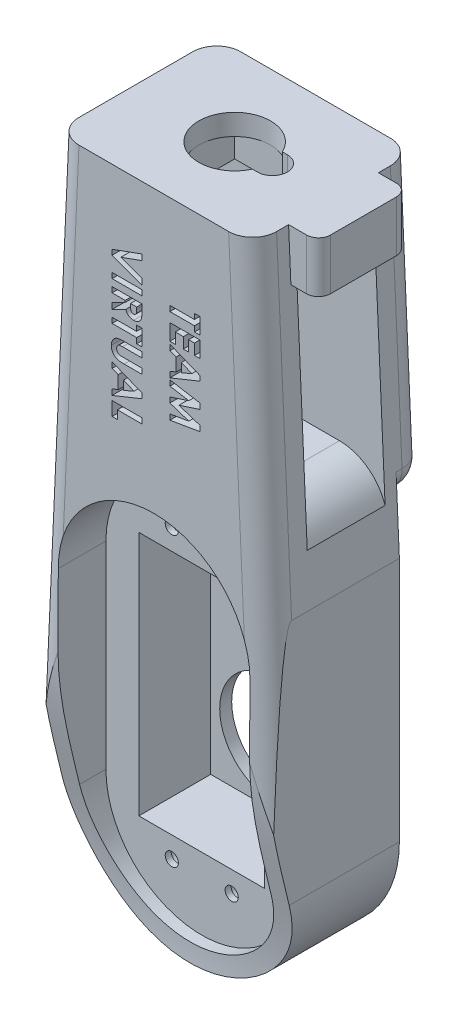
SolidWorks part; units mm, degrees
ref_plane "Front Plane" through (0, 0, 0) normal (0, 0, 1) x (1, 0, 0)
ref_plane "Top Plane" through (0, 0, 0) normal (0, 1, 0) x (1, 0, 0)
ref_plane "Right Plane" through (0, 0, 0) normal (1, 0, 0) x (0, 0, -1)
sketch "Sketch1" plane through (0, 0, 0) normal (0, 0, 1) x (1, 0, 0)
  line L5 (-19, -60) -> (19, -60)
  line L6 (-19, -60) -> (-19, 60)
  line L7 (-19, 60) -> (19, 60)
  line L8 (19, -60) -> (19, 60)
  line L9 (-19, -60) -> (19, 60) construction
  line L10 (-19, 60) -> (19, -60) construction
  line L11 (-10.5, -45) -> (10.5, -45)
  line L12 (-10.5, -45) -> (-10.5, -4)
  line L13 (-10.5, -4) -> (10.5, -4)
  line L14 (10.5, -45) -> (10.5, -4)
  line L15 (-10.5, -45) -> (10.5, -4) construction
  line L16 (-10.5, -4) -> (10.5, -45) construction
  point P0 (0, 0)
  point P6 (0, -24.5)
  dimension "D1" = 21
  dimension "D2" = 41
  dimension "D3" = 8.5
  dimension "D4" = 120
  dimension "D5" = 15
extrude "Boss-Extrude1" add sketch "Sketch1" along normal blind 11
ref_plane "Plane1" through (0, 0, 10) normal (0, 0, 1) x (1, 0, 0)
sketch "Sketch3" plane through (0, 0, 10) normal (0, 0, 1) x (1, 0, 0)
  line L0 (10.5, -4) -> (-10.5, -4) construction
  circle A0 centre (-5, -0.5) radius 1.3
  circle A1 centre (5, -0.5) radius 1.3
  circle A2 centre (5, -48.5) radius 1.3
  circle A3 centre (-5, -48.5) radius 1.3
  dimension "D1" = 2.6
  dimension "D2" = 5
  dimension "D3" = 3.5
  dimension "D4" = 2
  dimension "D5" = 2
extrude "Cut-Extrude1" cut sketch "Sketch3" against normal blind 8
fillet "Fillet3" radius 19 2 edges at (19, -60, 5.5) (-19, -60, 5.5)
sketch "Sketch4" plane through (0, 0, 11) normal (0, 0, 1) x (1, 0, 0)
  line L0 (16, -41) -> (16, 57)
  line L1 (16, 57) -> (-16, 57)
  line L2 (-16, 57) -> (-16, -41)
  line L3 (19, -41) -> (19, 60)
  line L4 (19, 60) -> (-19, 60)
  line L5 (-19, 60) -> (-19, -41)
  line L6 (19, -41) -> (19, 60)
  line L7 (19, 60) -> (-19, 60)
  line L8 (-19, 60) -> (-19, -41)
  arc A0 (-16, -41) -> (0, -57) centre (0, -41) ccw
  arc A1 (0, -57) -> (16, -41) centre (0, -41) ccw
  arc A2 (-19, -41) -> (0, -60) centre (0, -41) ccw
  arc A3 (0, -60) -> (19, -41) centre (0, -41) ccw
  arc A4 (-19, -41) -> (0, -60) centre (0, -41) ccw
  arc A5 (0, -60) -> (19, -41) centre (0, -41) ccw
  dimension "D1" = 0
  dimension "D2" = 3
extrude "Boss-Extrude2" add sketch "Sketch4" along normal blind 8
sketch "Sketch6" plane through (0, 0, 0) normal (1, 0, 0) x (0, 0, -1)
  line L7 (-13, -60) -> (-17, -35)
  line L8 (-17, -35) -> (-19, -20)
  line L9 (-19, -41) -> (-19, 60) construction
  line L10 (-19, -20) -> (-19, -60)
  line L11 (-19, -41) -> (-19, -60) construction
  line L12 (-19, -60) -> (-13, -60)
  line L13 (-11, -60) -> (0, -60) construction
  spline S0 degree 3 poles (-19, -20) (-18.8828, -33.6175) (-12.1748, -46.2563) (-13, -60) knots 0 0 0 0 1 1 1 1
  dimension "D1" = 6
  dimension "D2" = 25
  dimension "D3" = 15
  dimension "D4" = 2
extrude "Cut-Extrude2" cut sketch "Sketch6" against normal through all both and the other way through all contours L8 L7 | L10 L12 L7 L8 region at (0, -47.6101, 16.9935) region at (0, -47.9061, 14.5246)
sketch "Sketch7" plane through (0, 0, 11) normal (0, 0, 1) x (1, 0, 0)
  line L0 (16, -20) -> (16, 57) construction
  line L1 (16, 8) -> (-16, 8)
  line L2 (16, 8) -> (16, 57)
  line L3 (16, 57) -> (-16, 57)
  line L4 (-16, 8) -> (-16, 57)
  dimension "D1" = 49
extrude "Boss-Extrude4" add sketch "Sketch7" along normal up to surface (8 mm away) up to face at (0, 19.25, 19)
sketch "Sketch8" plane through (0, 0, 0) normal (0, 0, -1) x (-1, 0, 0)
  line L0 (-19, 60) -> (19, 60)
  line L1 (19, 60) -> (19, -6.3108)
  line L2 (19, 60) -> (19, -41) construction
  line L3 (-19, 60) -> (-19, -7)
  line L4 (-19, -41) -> (-19, 60) construction
  line L7 (19, 8) -> (-19, 8)
  arc A0 (19, -6.3108) -> (-19, -7) centre (0.25, -20.4388) ccw
  line M2 (-19, 60) -> (-19, -41)
  line M6 (19, 60) -> (-19, 60)
  dimension "D1" = 23.4769
  dimension "D2" = 67
  dimension "D3" = 19.25
  dimension "D4" = 52
extrude "Boss-Extrude5" add sketch "Sketch8" along normal blind 8 contours L7 L1 M6 M2 region at (0, 34, 0)
sketch "Sketch24" plane through (0, 0, 0) normal (0, 0, -1) x (-1, 0, 0)
  line L0 (10.5, -45) -> (-10.5, -45) construction
  line L3 (-19, 8) -> (-19, -41)
  line L4 (19, -41) -> (19, 8)
  line L5 (19, 8) -> (-19, 8)
  line L6 (-19, 8) -> (-19, -41)
  line L7 (19, -41) -> (19, 8)
  line L10 (19, 8) -> (-19, 8)
  circle A0 centre (0, -34.75) radius 9
  arc A2 (-19, -41) -> (0, -60) centre (0, -41) ccw
  arc A3 (0, -60) -> (19, -41) centre (0, -41) ccw
  arc A4 (-19, -41) -> (0, -60) centre (0, -41) ccw
  arc A5 (0, -60) -> (19, -41) centre (0, -41) ccw
  dimension "D2" = 18
  dimension "D3" = 10.25
  dimension "D1" = 0
extrude "Boss-Extrude6" add sketch "Sketch24" along normal blind 3
fillet "Fillet4" radius 16 2 edges at (-16, 8, 15) (16, 8, 15)
sketch "Sketch26" plane through (0, 60, 0) normal (0, 1, 0) x (1, 0, 0)
  line L4 (19, -19) -> (19, 8)
  line L5 (19, 8) -> (-19, 8)
  line L6 (-19, 8) -> (-19, -19)
  line L7 (-19, -19) -> (19, -19)
  line L8 (19, -19) -> (19, 8)
  line L9 (19, 8) -> (-19, 8)
  line L10 (-19, 8) -> (-19, -19)
  line L11 (-19, -19) -> (19, -19)
  dimension "D1" = 0
extrude "Cut-Extrude4" cut sketch "Sketch26" against normal blind 5
sketch "Sketch27" plane through (19, 0, 0) normal (1, 0, 0) x (0, 0, -1)
  line L0 (-19, 55) -> (8, 55) construction
  line L1 (-12, 45) -> (1, 45)
  line L2 (-12, 45) -> (-12, 14)
  line L3 (-12, 14) -> (1, 14)
  line L4 (1, 45) -> (1, 14)
  line L5 (-19, -20) -> (-19, 55) construction
  dimension "D1" = 10
  dimension "D2" = 31
  dimension "D3" = 13
  dimension "D4" = 7
extrude "Cut-Extrude5" cut sketch "Sketch27" against normal through all
sketch "Sketch29" plane through (0, 45, 0) normal (0, -1, 0) x (1, 0, 0)
  line L7 (-19, -1) -> (19, -1)
  line L8 (19, -1) -> (19, 12)
  line L9 (19, 19) -> (19, -8) construction
  line L10 (19, 12) -> (-19, 12)
  line L11 (-19, 12) -> (-19, -1)
extrude "Cut-Extrude7" cut sketch "Sketch29" against normal blind 1.5
sketch "Sketch28" plane through (0, 55, 0) normal (0, 1, 0) x (1, 0, 0)
  line L0 (-19, 8) -> (-19, -19) construction
  line L1 (19, 8) -> (-19, 8) construction
  line L2 (0, -5.5) -> (8.8, -5.5)
  line L3 (6.3, -3) -> (5.4544, -3)
  line L4 (6.3, -8) -> (5.4544, -8)
  arc A0 (5.4544, -3) -> (5.4544, -8) centre (0, -5.5) ccw
  arc A1 (6.3, -8) -> (6.3, -3) centre (6.3, -5.5) ccw
  dimension "D1" = 12
  dimension "D4" = 6.3
  dimension "D2" = 19
  dimension "D3" = 13.5
extrude "Cut-Extrude8" cut sketch "Sketch28" against normal blind 3.5 contours A0 L4 A1 L3
fillet "Fillet6" radius 8 2 edges at (-19, 14, 5.5) (19, 14, 5.5)
sketch "Sketch31" plane through (0, 0, 11) normal (0, 0, 1) x (1, 0, 0)
  line L0 (10.5, -4) -> (-10.5, -4) construction
  circle A0 centre (-5, -0.5) radius 1.1
  circle A1 centre (5, -0.5) radius 1.1
  circle A2 centre (5, -48.5) radius 1.1
  circle A3 centre (-5, -48.5) radius 1.1
  dimension "D1" = 2.2
  dimension "D2" = 3.5
  dimension "D3" = 5
  dimension "D4" = 2
  dimension "D5" = 2
extrude "Cut-Extrude10" cut sketch "Sketch31" against normal blind 8
sketch "Sketch34" plane through (0, 0, 19) normal (0, 0, 1) x (1, 0, 0)
  line L0 (16.5, 55) -> (19, 0)
  line L1 (-19, 55) -> (19, 55) construction
  line L2 (19, -20) -> (19, 55) construction
  line L3 (19, 0) -> (19, 55)
  line L4 (19, 55) -> (16.5, 55)
  line L5 (-16.5, 55) -> (-19, 0)
  line L6 (-19, 55) -> (-19, -20) construction
  line L7 (-19, 0) -> (-19, 55)
  line L8 (-19, 55) -> (-16.5, 55)
  dimension "D1" = 2.5
  dimension "D2" = 2.5
  dimension "D3" = 55
  dimension "D4" = 55
extrude "Cut-Extrude13" cut sketch "Sketch34" against normal through all
fillet "Fillet11" radius 4 4 edges at (-17.5682, 31.5, -8) (-17.75, 27.5, 19) (17.5682, 31.5, -8) (17.75, 27.5, 19)
sketch "Sketch35" plane through (0, 0, 19) normal (0, 0, 1) x (1, 0, 0)
  line L0 (2.684, 8) -> (2.684, 55) construction
  text T0 "<b>TEAM</b>\r\n<b>VIRTUAL</b>" font "Century Gothic" height 5
extrude "Cut-Extrude14" cut sketch "Sketch35" against normal blind 5
fillet "Fillet12" radius 4 5 edges at (-18.6364, 8, -3.5) (-17.4636, 8, -6.8284) (18.6364, 8, -3.5) (17.4636, 8, -6.8284) (0, 8, -8)
sketch "Sketch39" plane through (0, 46.5, 0) normal (0, -1, 0) x (1, 0, 0)
  line L3 (-6, -0.5) -> (0, -0.5)
  line L4 (0, -0.5) -> (16.5, -0.5)
  line L5 (16.5, -4) -> (16.5, 15) construction
  line L7 (16.5, 11.4993) -> (0.0905, 11.4993)
  line L8 (-6, 11.5) -> (-6, -0.5)
  line L9 (16.5, 5.5) -> (16.6, 5.5)
  line L12 (16.5, 11.4993) -> (21.3, 11.4993)
  line L13 (21.3, 11.4993) -> (21.3, -0.5)
  line L14 (21.3, -0.5) -> (16.5, -0.5)
  line L15 (0.0905, 11.4993) -> (-6, 11.5)
  arc A0 (5.4544, 8) -> (5.4544, 3) centre (0, 5.5) ccw construction
  arc A1 (5.4544, 8) -> (5.4544, 3) centre (0, 5.5) ccw construction
extrude "Cut-Extrude16" cut sketch "Sketch39" against normal blind 5 contours L7 L15 L8 L3 L4 L14 L12 region at (5.4431, 46.5, 5.4997)
sketch "Sketch40" plane through (0, 55, 0) normal (0, 1, 0) x (1, 0, 0)
  line L6 (16.5, -5.5) -> (16.5, -13)
  line L7 (16.5, 4) -> (16.5, -15) construction
  line L8 (16.5, -13) -> (21.5, -13)
  line L9 (21.5, -13) -> (21.5, 2)
  line L10 (21.5, 2) -> (16.5, 2)
  line L11 (16.5, 2) -> (16.5, -5.5)
extrude "Boss-Extrude8" add sketch "Sketch40" against normal blind 8.5
sketch "Sketch32" plane through (0, 46.5, 0) normal (0, -1, 0) x (1, 0, 0)
  line L0 (0, 5.5) -> (-8.5, 5.5)
  line L2 (0, 5.5) -> (19, 5.5)
  circle A0 centre (19, 5.5) radius 1.1
  circle A1 centre (-8.5, 5.5) radius 1.1
  dimension "D1" = 2.2
  dimension "D2" = 2.2
extrude "Cut-Extrude11" cut sketch "Sketch32" against normal mid plane 5 contours A0 | A1
fillet "Fillet13" radius 2 2 edges at (21.5, 50.75, -2) (21.5, 50.75, 13)
sketch "Sketch43" plane through (0, 0, 0) normal (0, 0, 1) x (1, 0, 0)
  line L0 (-10.5, -45) -> (-10.5, -4)
  line L1 (-10.5, -4) -> (10.5, -4)
  line L2 (10.5, -4) -> (10.5, -45)
  line L3 (10.5, -45) -> (-10.5, -45)
extrude "Cut-Extrude17" cut sketch "Sketch43" against normal blind 1
